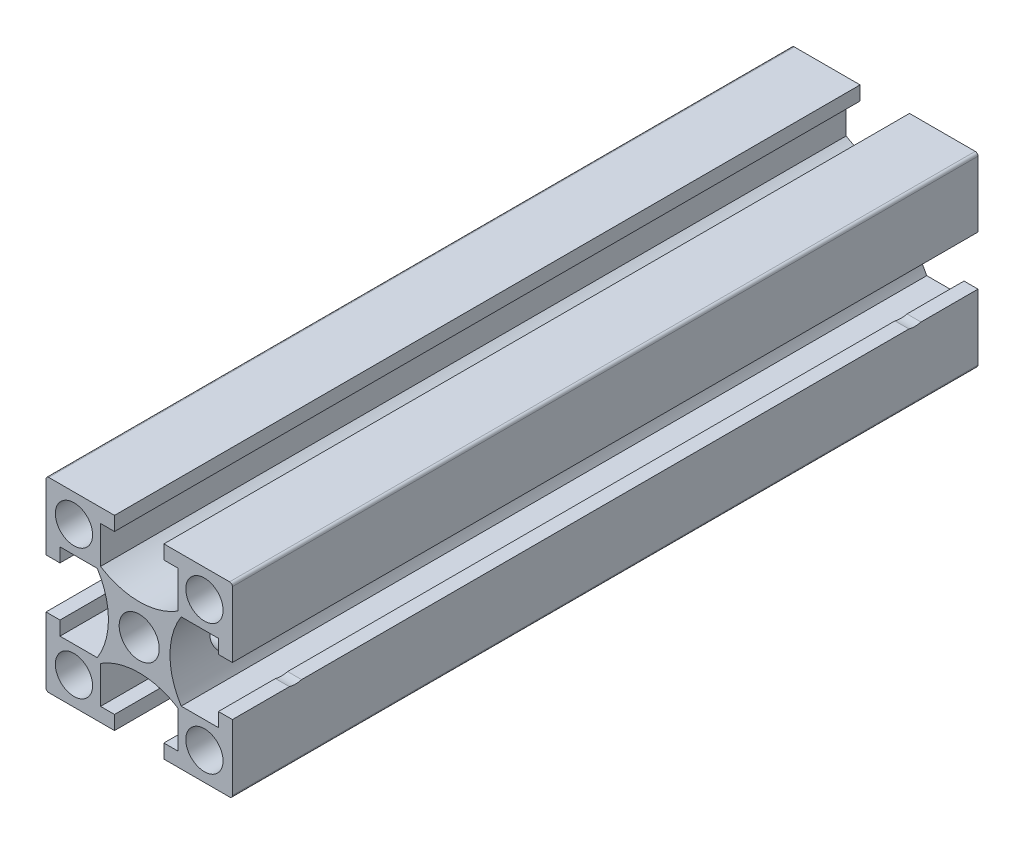
SolidWorks part; units mm, degrees
material "3.0255 (EN-AW 1350A)"
ref_plane "정면" through (0, 0, 0) normal (0, 0, 1) x (1, 0, 0)
ref_plane "윗면" through (0, 0, 0) normal (0, 1, 0) x (1, 0, 0)
ref_plane "우측면" through (0, 0, 0) normal (1, 0, 0) x (0, 0, -1)
sketch "스케치1" plane through (0, 0, 0) normal (0, 0, 1) x (1, 0, 0)
  line L0 (0, 32.0265) -> (0, -31.6588) construction
  line L1 (-10, 10) -> (-10, -10)
  line L2 (-10, 10) -> (10, 10)
  line L3 (-10, 2.65) -> (-8.5, 2.65)
  line L4 (13.6618, 0) -> (-11.6993, 0) construction
  line L5 (-8.5, 2.65) -> (-8.5, 4.15)
  line L6 (-8.5, 4.15) -> (-4.5032, 4.15)
  line L7 (-10, -2.65) -> (-8.5, -2.65)
  line L8 (-8.5, -2.65) -> (-8.5, -4.15)
  line L9 (-8.5, -4.15) -> (-4.5032, -4.15)
  line L10 (-10, -10) -> (10, -10)
  line L11 (10, 10) -> (10, -10)
  circle A0 centre (-7, 7) radius 2
  circle A1 centre (-7, -7) radius 2
  arc A2 (-4.5032, 4.15) -> (-4.5032, -4.15) centre (-11.0587, 0) cw
  circle A3 centre (0, 0) radius 2.15
  circle A4 centre (7, 7) radius 2
  circle A5 centre (7, -7) radius 2
  point P21 (-10, 0)
  point P23 (-3.3, 0)
  point P31 (0, -10)
  point P32 (0, 10)
  dimension "D3" = 4
  dimension "D9" = 6.7
  dimension "D10" = 4.3
  dimension "D11" = 7.7587
  dimension "D1" = 20
  dimension "D2" = 20
  dimension "D4" = 14
  dimension "D5" = 14
  dimension "D6" = 5.3
  dimension "D7" = 8.3
  dimension "D8" = 1.5
extrude "보스-돌출1" add sketch "스케치1" along normal blind 80 contours A0 | A4 | A3 | A5 | A1 | A2 L6 L5 L3 L1 L7 L8 L9 | L2 L11 L10 L1 region at (-6.6069, 0, 0) region at (-7, 7, 0) region at (-7, -7, 0) region at (0, 0, 0) region at (7, 7, 0) region at (7, -7, 0)
extrude "컷-돌출1" cut sketch "스케치1<3>" along normal up to next contours A2 L6 L5 L3 L1 L7 L8 L9 region at (-6.6069, 0, 0)
sketch "스케치1<3>" plane through (0, 0, 0) normal (0, 0, 1) x (1, 0, 0) same geometry as "스케치1"
pattern_circular "원형 패턴1" count 4 over 360 about axis through (0, 0, 80) along (0, 0, -1) of "컷-돌출1" reverse direction yes
fillet "필렛1" radius 0.3 4 edges at (10, -10, 40) (-10, -10, 40) (-10, 10, 40) (10, 10, 40)
sketch "스케치3" plane through (0, -10, 0) normal (0, -1, 0) x (1, 0, 0)
  line L0 (4.15, 80) -> (-4.15, 80) construction
  circle A0 centre (0, 70) radius 2.5
  dimension "D1" = 10
extrude "컷-돌출2" cut sketch "스케치3" against normal through all
sketch "스케치4" plane through (-10, 0, 0) normal (-1, 0, 0) x (0, 0, 1)
  line L0 (0, -2.65) -> (0, -9.7) construction
  line L5 (80, -10) -> (0, -10)
  line L6 (80, -10) -> (80, -7)
  line L7 (80, -7) -> (0, -7)
  line L8 (0, -10) -> (0, -7)
  line L9 (0, -7) -> (80, 72.9955) construction
  line L10 (80, -7) -> (0, -7)
  line L11 (80, -7) -> (80, 72.9955)
  line L12 (80, 72.9955) -> (0, 72.9955)
  line L13 (0, -7) -> (0, 72.9955)
  circle A5 centre (40, 32.9977) radius 47
  circle A6 centre (6.765, -0.2353) radius 2.5
  circle A7 centre (6.7669, 66.2327) radius 2.5
  circle A8 centre (73.235, 66.2308) radius 2.5
  circle A9 centre (73.2331, -0.2372) radius 2.5
  point P21 (40, 32.9977)
  dimension "D2" = 4
  dimension "D3" = 5
  dimension "D1" = 3
extrude "컷-돌출4" cut sketch "스케치4" against normal through all contours A6 | A9
